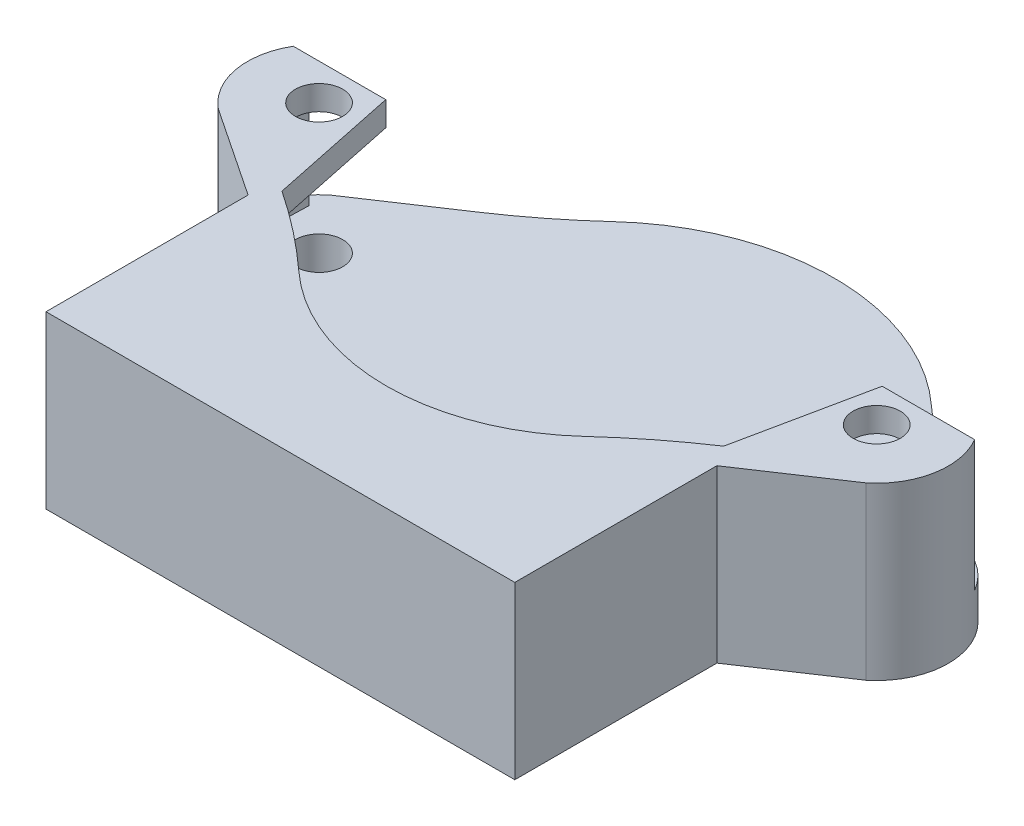
SolidWorks part; units mm, degrees
ref_plane "Front Plane" through (0, 0, 0) normal (0, 0, 1) x (1, 0, 0)
ref_plane "Top Plane" through (0, 0, 0) normal (0, 1, 0) x (1, 0, 0)
ref_plane "Right Plane" through (0, 0, 0) normal (1, 0, 0) x (0, 0, -1)
sketch "Sketch1" plane through (0, 0, 0) normal (0, 1, 0) x (1, 0, 0)
  line L0 (62.9004, 19.0691) -> (73.8872, 26.3996)
  line L6 (62.9004, 47.4193) -> (73.8872, 40.0888)
  line L7 (5.3122, 47.4193) -> (-5.6747, 40.0888)
  line L8 (5.3122, 19.0691) -> (-5.6747, 26.3996)
  circle A4 centre (68.3563, 33.2442) radius 2.9
  circle A9 centre (-0.1437, 33.2442) radius 2.9
  arc A12 (73.8872, 26.3996) -> (73.8872, 40.0888) centre (68.3563, 33.2442) ccw
  arc A13 (53.6758, 54.6459) -> (62.9004, 47.4193) centre (105.6362, 111.4712) ccw
  arc A14 (53.6758, 54.6459) -> (14.5367, 54.6459) centre (34.1063, 33.2442) ccw
  arc A15 (14.5367, 54.6459) -> (5.3122, 47.4193) centre (-37.4237, 111.4712) cw
  arc A16 (-5.6747, 26.3996) -> (-5.6747, 40.0888) centre (-0.1437, 33.2442) cw
  arc A17 (14.5367, 11.8425) -> (5.3122, 19.0691) centre (-37.4237, -44.9828) ccw
  arc A18 (14.5367, 11.8425) -> (53.6758, 11.8425) centre (34.1063, 33.2442) ccw
  arc A19 (53.6758, 11.8425) -> (62.9004, 19.0691) centre (105.6362, -44.9828) cw
extrude "Boss-Extrude1" add sketch "Sketch1" along normal blind 5
sketch "Sketch3" plane through (0, 5, 0) normal (0, 1, 0) x (1, 0, 0)
  line L0 (62.9004, 19.0691) -> (73.8872, 26.3996)
  line L1 (61.2354, 21.5647) -> (72.0964, 28.8112)
  line L2 (6.9772, 21.5647) -> (-3.8838, 28.8112)
  line L3 (5.3122, 19.0691) -> (-5.6747, 26.3996)
  line L4 (74.0272, 37.6772) -> (75.9581, 37.6772)
  line L5 (-5.8147, 37.6772) -> (-7.7456, 37.6772)
  line L6 (-5.9437, 33.2442) -> (-5.8147, 37.6772)
  line L8 (74.1563, 33.2442) -> (74.0272, 37.6772)
  arc A0 (16.5612, 14.0565) -> (51.6514, 14.0565) centre (34.1063, 33.2442) ccw
  arc A2 (72.0964, 28.8112) -> (74.1563, 33.2442) centre (68.3563, 33.2442) ccw
  arc A3 (51.6514, 14.0565) -> (61.2354, 21.5647) centre (105.6362, -44.9828) cw
  arc A4 (-3.8838, 28.8112) -> (-5.9437, 33.2442) centre (-0.1437, 33.2442) cw
  arc A6 (16.5612, 14.0565) -> (6.9772, 21.5647) centre (-37.4237, -44.9828) ccw
  arc A7 (73.8872, 26.3996) -> (75.9581, 37.6772) centre (68.3563, 33.2442) ccw
  arc A8 (-5.6747, 26.3996) -> (-7.7456, 37.6772) centre (-0.1437, 33.2442) cw
  arc A9 (14.5367, 11.8425) -> (5.3122, 19.0691) centre (-37.4237, -44.9828) ccw
  arc A10 (14.5367, 11.8425) -> (53.6758, 11.8425) centre (34.1063, 33.2442) ccw
  arc A11 (53.6758, 11.8425) -> (62.9004, 19.0691) centre (105.6362, -44.9828) cw
extrude "Boss-Extrude2" add sketch "Sketch3" along normal blind 13
sketch "Sketch4" plane through (0, 18, 0) normal (0, 1, 0) x (1, 0, 0)
  line L0 (3.6162, 37.6772) -> (-7.7456, 37.6772)
  line L1 (62.9004, 19.0691) -> (73.8872, 26.3996)
  line L4 (5.3122, 19.0691) -> (-5.6747, 26.3996)
  line L11 (3.6162, 37.6772) -> (6.9772, 21.5647)
  line L12 (64.5964, 37.6772) -> (61.2354, 21.5647)
  line L13 (64.5964, 37.6772) -> (75.9581, 37.6772)
  arc A3 (16.5612, 14.0565) -> (51.6514, 14.0565) centre (34.1063, 33.2442) ccw
  arc A6 (51.6514, 14.0565) -> (61.2354, 21.5647) centre (105.6362, -44.9828) cw
  arc A9 (16.5612, 14.0565) -> (6.9772, 21.5647) centre (-37.4237, -44.9828) ccw
  arc A10 (73.8872, 26.3996) -> (75.9581, 37.6772) centre (68.3563, 33.2442) ccw
  arc A11 (-5.6747, 26.3996) -> (-7.7456, 37.6772) centre (-0.1437, 33.2442) cw
  arc A12 (14.5367, 11.8425) -> (5.3122, 19.0691) centre (-37.4237, -44.9828) ccw
  arc A13 (14.5367, 11.8425) -> (53.6758, 11.8425) centre (34.1063, 33.2442) ccw
  arc A14 (53.6758, 11.8425) -> (62.9004, 19.0691) centre (105.6362, -44.9828) cw
  circle A15 centre (-0.1437, 33.2442) radius 2.9
  circle A16 centre (68.3563, 33.2442) radius 2.9
extrude "Boss-Extrude3" add sketch "Sketch4" along normal blind 3
sketch "Sketch5" plane through (0, 0, 0) normal (0, -1, 0) x (1, 0, 0)
  line L7 (62.9004, -19.0691) -> (62.9004, 5.7558)
  line L8 (62.9004, 5.7558) -> (5.3122, 5.7558)
  line L9 (5.3122, 5.7558) -> (5.3122, -19.0691)
  arc A15 (14.5367, -11.8425) -> (5.3122, -19.0691) centre (-37.4237, 44.9828) cw
  arc A17 (53.6758, -11.8425) -> (62.9004, -19.0691) centre (105.6362, 44.9828) ccw
  arc A19 (14.5367, -11.8425) -> (53.6758, -11.8425) centre (34.1063, -33.2442) cw
extrude "Boss-Extrude4" add sketch "Sketch5" against normal blind 21
